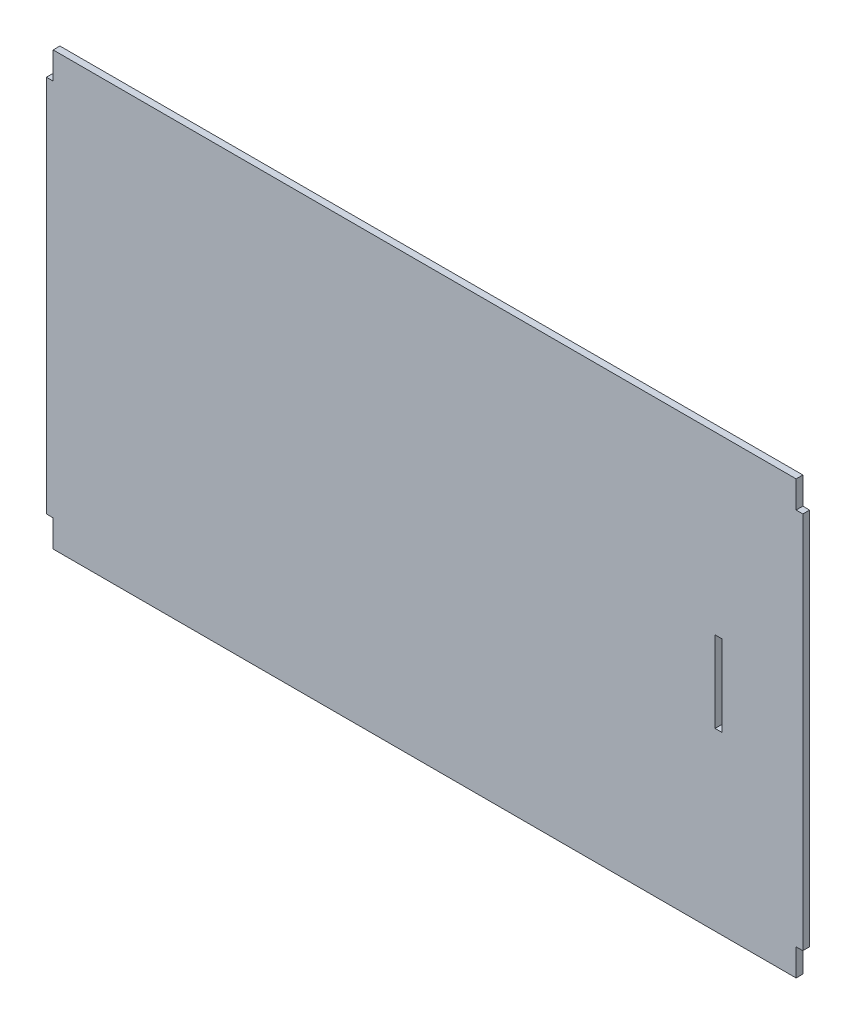
SolidWorks part; units mm, degrees
ref_plane "Front Plane" through (0, 0, 0) normal (0, 0, 1) x (1, 0, 0)
ref_plane "Top Plane" through (0, 0, 0) normal (0, 1, 0) x (1, 0, 0)
ref_plane "Right Plane" through (0, 0, 0) normal (1, 0, 0) x (0, 0, -1)
sketch "Sketch1" plane through (0, 0, 0) normal (0, 0, 1) x (1, 0, 0)
  line L0 (3.175, 203.2) -> (3.175, 190.5)
  line L1 (3.175, 0) -> (352.425, 0)
  line L2 (0, 12.7) -> (0, 190.5)
  line L3 (3.175, 203.2) -> (352.425, 203.2)
  line L4 (355.6, 12.7) -> (355.6, 190.5)
  line L5 (3.175, 190.5) -> (0, 190.5)
  line L6 (3.175, 12.7) -> (0, 12.7)
  line L7 (3.175, 12.7) -> (3.175, 0)
  line L8 (352.425, 0) -> (352.425, 12.7)
  line L9 (352.425, 12.7) -> (355.6, 12.7)
  line L10 (352.425, 203.2) -> (352.425, 190.5)
  line L11 (352.425, 190.5) -> (355.6, 190.5)
  dimension "D1" = 355.6
  dimension "D3" = 12.7
  dimension "D4" = 12.7
  dimension "D5" = 12.7
  dimension "D6" = 12.7
  dimension "D7" = 3.175
  dimension "D8" = 3.175
  dimension "D9" = 3.175
extrude "Shelf" add sketch "Sketch1" along normal blind 3.175
sketch "Tilt mount slot sketch" plane through (0, 0, 3.175) normal (0, 0, 1) x (1, 0, 0)
  line L1 (317.5, 120.65) -> (317.5, 203.2) construction
  line L2 (317.5, 120.65) -> (314.325, 120.65)
  line L3 (317.5, 120.65) -> (317.5, 82.55)
  line L4 (317.5, 82.55) -> (314.325, 82.55)
  line L5 (314.325, 120.65) -> (314.325, 82.55)
  line L6 (352.425, 203.2) -> (3.175, 203.2) construction
  line L7 (317.5, 82.55) -> (317.5, 0) construction
  line L8 (3.175, 0) -> (352.425, 0) construction
  line L9 (355.6, 12.7) -> (355.6, 190.5) construction
  point P8 (0, 0)
  dimension "D1" = 3.175
  dimension "D2" = 38.1
  dimension "D3" = 38.1
extrude "Tilt Mount Slot" cut sketch "Tilt mount slot sketch" against normal through all
